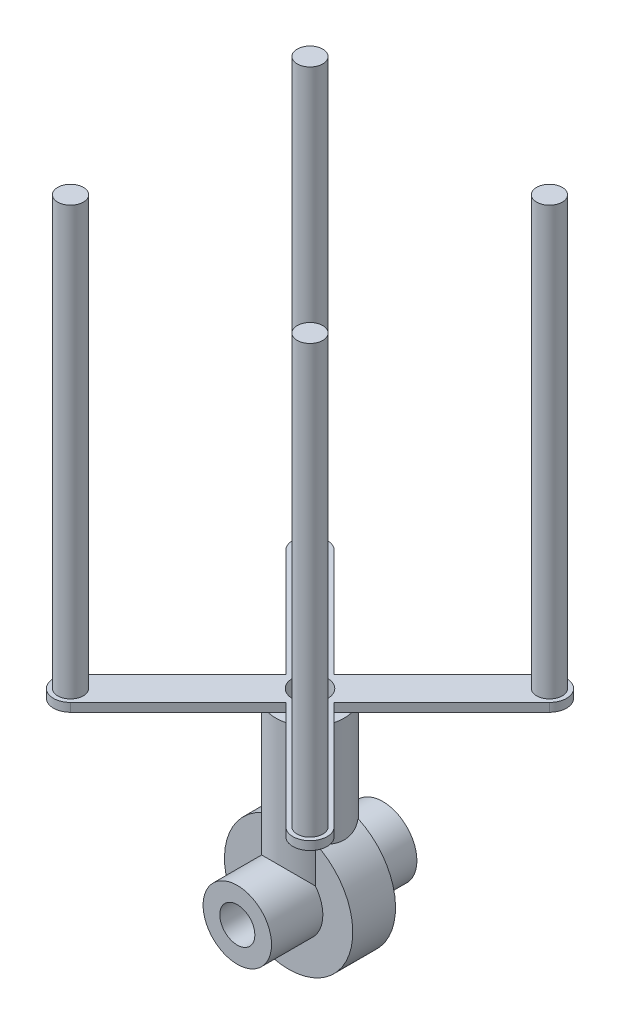
SolidWorks part; units mm, degrees
ref_plane "Front Plane" through (0, 0, 0) normal (0, 0, 1) x (1, 0, 0)
ref_plane "Top Plane" through (0, 0, 0) normal (0, 1, 0) x (1, 0, 0)
ref_plane "Right Plane" through (0, 0, 0) normal (1, 0, 0) x (0, 0, -1)
sketch "Sketch1" plane through (0, 0, 0) normal (0, 0, 1) x (1, 0, 0)
  circle A0 centre (102.3412, 36.4161) radius 7.5
  circle A1 centre (102.3412, 36.4161) radius 2.05
extrude "Boss-Extrude1" add sketch "Sketch1" along normal blind 2.5
sketch "Sketch2" plane through (0, 0, 2.5) normal (0, 0, 1) x (1, 0, 0)
  circle A0 centre (102.3412, 36.4161) radius 2.05
  circle A1 centre (102.3412, 36.4161) radius 4
extrude "Boss-Extrude2" add sketch "Sketch2" along normal blind 6
sketch "Sketch7" plane through (0, 0, 0) normal (0, 0, -1) x (-1, 0, 0)
  line L1 (-106.3412, 36.4161) -> (-102.3412, 36.4161)
  line L2 (-106.3412, 36.4161) -> (-106.3412, 55.1033)
  line L3 (-106.3412, 55.1033) -> (-102.3412, 55.1033)
  line L4 (-102.3412, 36.4161) -> (-102.3412, 55.1033)
  point P6 (0, 0)
  point P7 (-102.3412, 36.4161)
  point P9 (0, 0)
revolve "Revolve7" add sketch "Sketch7" angle 180 about L4 reverse direction yes
sketch "Sketch8" plane through (0, 0, 0) normal (0, 0, -1) x (-1, 0, 0)
  line L0 (-104.3912, 36.4161) -> (-100.2912, 36.4161) construction
  line L1 (-102.3412, 36.4161) -> (-104.3912, 36.4161)
  line L2 (-102.3412, 36.4161) -> (-102.3412, 55.1033)
  line L3 (-102.3412, 55.1033) -> (-104.3912, 55.1033)
  line L4 (-104.3912, 36.4161) -> (-104.3912, 55.1033)
  line L5 (-98.3412, 55.1033) -> (-106.3412, 55.1033) construction
revolve "Cut-Revolve2" cut sketch "Sketch8" angle 360 about L2
sketch "Sketch9" plane through (0, 0, 0) normal (0, 0, -1) x (-1, 0, 0)
  circle A0 centre (-102.3412, 36.4161) radius 2.05
extrude "Cut-Extrude1" cut sketch "Sketch9" against normal blind 5
mirror "Mirror1" about plane through (102.3412, 36.4161, 0) normal (0, 0, 1) of "Cut-Extrude1", "Revolve7", "Boss-Extrude2", "Boss-Extrude1", "Cut-Revolve2"
sketch "Sketch10" plane through (0, 55.1033, 0) normal (0, 1, 0) x (1, 0, 0)
  line L0 (102.3412, 0) -> (88.3412, 14) construction
  line L1 (121.3412, -19) -> (83.3412, -19) construction
  line L2 (121.3412, -19) -> (121.3412, 19) construction
  line L3 (121.3412, 19) -> (83.3412, 19) construction
  line L4 (83.3412, -19) -> (83.3412, 19) construction
  line L5 (121.3412, -19) -> (83.3412, 19) construction
  line L6 (121.3412, 19) -> (83.3412, -19) construction
  line L11 (102.3412, 0) -> (116.3412, 14) construction
  line L14 (102.3412, 0) -> (116.3412, -14) construction
  line L17 (102.3412, 0) -> (88.3412, -14) construction
  line L20 (102.3412, 2.8284) -> (89.7554, 15.4142)
  line L21 (105.1696, 0) -> (117.7554, -12.5858)
  line L22 (105.1696, 0) -> (117.7554, 12.5858)
  line L23 (102.3412, -2.8284) -> (89.7554, -15.4142)
  line L24 (102.3412, -2.8284) -> (114.927, -15.4142)
  line L25 (99.5128, 0) -> (86.927, 12.5858)
  line L26 (99.5128, 0) -> (86.927, -12.5858)
  line L27 (102.3412, 2.8284) -> (114.927, 15.4142)
  arc A4 (89.7554, 15.4142) -> (86.927, 12.5858) centre (88.3412, 14) ccw
  arc A6 (117.7554, 12.5858) -> (114.927, 15.4142) centre (116.3412, 14) ccw
  arc A8 (114.927, -15.4142) -> (117.7554, -12.5858) centre (116.3412, -14) ccw
  arc A10 (86.927, -12.5858) -> (89.7554, -15.4142) centre (88.3412, -14) ccw
  circle A11 centre (102.3412, 0) radius 2.05
  point P0 (102.3412, 0)
  point P8 (95.3412, 7)
  point P18 (109.3412, 7)
  point P25 (109.3412, -7)
  point P32 (95.3412, -7)
  point P38 (102.3412, 0)
  dimension "D1" = 38
  dimension "D2" = 38
  dimension "D3" = 5
  dimension "D4" = 5
extrude "Boss-Extrude3" add sketch "Sketch10" along normal blind 1
sketch "Sketch11" plane through (0, 56.1033, 0) normal (0, 1, 0) x (1, 0, 0)
  circle A4 centre (88.3412, 14) radius 1.5
  circle A5 centre (116.3412, 14) radius 1.5
  circle A6 centre (116.3412, -14) radius 1.5
  circle A7 centre (88.3412, -14) radius 1.5
  point P11 (102.3412, 0)
extrude "Boss-Extrude4" add sketch "Sketch11" along normal blind 50
